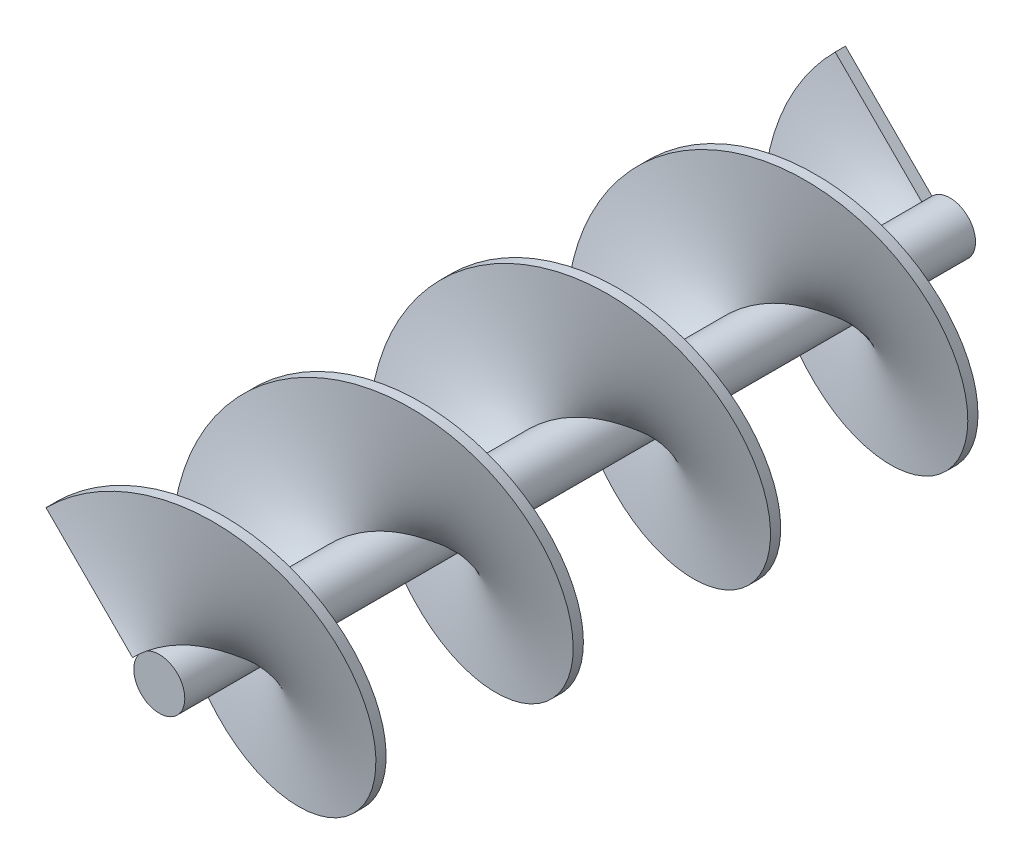
SolidWorks part; units mm, degrees
ref_plane "前视基准面" through (0, 0, 0) normal (0, 0, 1) x (1, 0, 0)
ref_plane "上视基准面" through (0, 0, 0) normal (0, 1, 0) x (1, 0, 0)
ref_plane "右视基准面" through (0, 0, 0) normal (1, 0, 0) x (0, 0, -1)
other "Configuration Table"
sketch "草图1" plane through (0, 0, 0) normal (0, 0, 1) x (1, 0, 0)
  circle A0 centre (0, 0) radius 5
  dimension "D1" = 10
extrude "凸台-拉伸1" add sketch "草图1" along normal blind 155
sketch "草图3" plane through (0, 0, 155) normal (0, 0, 1) x (1, 0, 0)
  circle A0 centre (0, 0) radius 5 construction
  circle A1 centre (0, 0) radius 5
curve "螺旋线/涡状线1" pitch 38.675 height 154.7 radius 5 centre (0, 0, 155) axis (0, 0, -1) start towards (-0.7071, 0.7071, 0)
ref_plane "基准面1" through (-3.5355, 3.5355, 0.3) normal (-0.7071, -0.7071, 0) x (0, 0, 1)
sketch "草图4" plane through (-3.5355, 3.5355, 0.3) normal (-0.7071, -0.7071, 0) x (0, 0, 1)
  line L0 (-0.3, 0) -> (-0.3, 24)
  line L1 (-0.3, 24) -> (1.7, 24)
  line L2 (1.7, 24) -> (1.7, 0)
  line L3 (154.7, 0) -> (-0.3, 0) construction
  line L4 (1.7, 0) -> (-0.3, 0)
  dimension "D1" = 24
  dimension "D2" = 2
sweep "扫描1" add profiles "草图4" path "螺旋线/涡状线1"
sketch "草图5" plane through (0, 0, 0) normal (0, 0, -1) x (-1, 0, 0)
  circle A0 centre (0, 0) radius 4
  dimension "D1" = 8
extrude "切除-拉伸1" cut sketch "草图5" against normal blind 8
